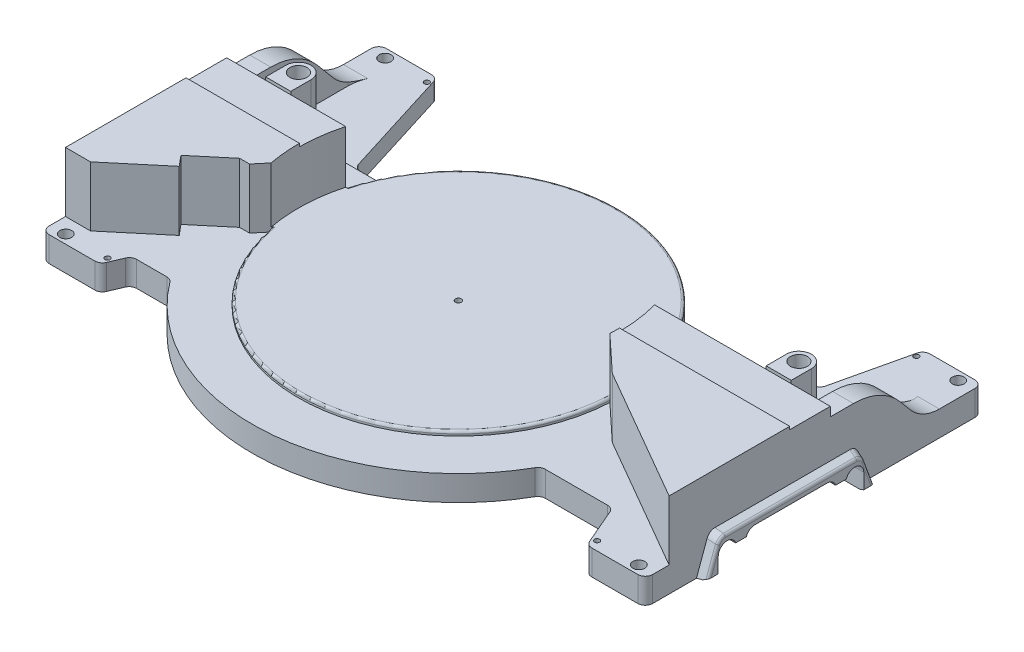
SolidWorks part; units mm, degrees
note: '?' marks a value the reader was unsure of.
ref_plane "Front Plane" through (0, 0, 0) normal (0, 0, 1) x (1, 0, 0)
ref_plane "Top Plane" through (0, 0, 0) normal (0, 1, 0) x (1, 0, 0)
ref_plane "Right Plane" through (0, 0, 0) normal (1, 0, 0) x (0, 0, -1)
sketch "Sketch1" plane through (0, 0, 0) normal (0, 1, 0) x (1, 0, 0)
  line L0 (330.2, 437.9007) -> (330.2, -96.542) construction
  line L1 (9.144, 0) -> (71.12, 0)
  line L3 (9.144, 358.648) -> (71.12, 358.648)
  line L7 (300.0375, 292.4565) -> (300.0375, 69.5569) construction
  line L8 (244.8786, 152.4) -> (359.3405, 152.4) construction
  line L9 (110.744, 231.648) -> (149.3493, 231.648)
  line L10 (450.7257, 231.648) -> (486.156, 231.648)
  line L11 (492.5022, 47.752) -> (568.706, 47.752)
  line L12 (651.256, 358.648) -> (651.256, 0)
  line L19 (9.144, 358.648) -> (9.144, 0)
  line L20 (81.28, 23.749) -> (122.7164, 23.749)
  line L21 (81.28, 23.749) -> (71.12, 0)
  line L22 (568.706, 47.752) -> (589.28, 0)
  line L23 (589.28, 358.648) -> (568.706, 269.748)
  line L24 (589.28, 0) -> (651.256, 0)
  line L25 (568.706, 269.748) -> (486.156, 231.648)
  line L26 (71.12, 358.648) -> (110.744, 231.648)
  line L27 (589.28, 358.648) -> (651.256, 358.648)
  arc A2 (450.7257, 231.648) -> (149.3493, 231.648) centre (300.0375, 152.4) ccw
  arc A3 (122.7164, 23.749) -> (492.5022, 47.752) centre (300.0375, 152.4) ccw
  point P4 (330.2, 179.324)
  dimension "D5" = 642.112
  dimension "D6" = 47.752
  dimension "D8" = 170.2562
  dimension "D4" = 219.075
  dimension "D2" = 358.648
  dimension "D7" = 127
  dimension "D9" = 290.8935
  dimension "D10" = 152.4
  dimension "D11" = 9.144
  dimension "D12" = 101.6
  dimension "D13" = 82.55
  dimension "D15" = 61.976
  dimension "D17" = 61.976
  dimension "D18" = 23.749
  dimension "D20" = 72.136
  dimension "D22" = 61.976
  dimension "D23" = 61.976
  dimension "D24" = 88.9
  dimension "D25" = 82.55
  dimension "D26" = 165.1
  dimension "D32" = 321.056
extrude "Boss-Extrude1" add sketch "Sketch1" along normal blind 20.6375
ref_axis "Axis1" through (300.0375, 49.3521, -152.4) along (0, -1, 0)?
ref_plane "Plane4" through (300.0375, 0, 0) normal (-1, 0, 0) x (0, -1, 0)
ref_plane "Plane5" through (73.8187, 0, 73.8187) normal (-0.7071, 0, -0.7071) x (0, -1, 0)
sketch "Sketch55" plane through (0, 0, 0) normal (0, -1, 0) x (1, 0, 0)
  line L0 (55, 0) -> (-55, 0) construction
  line L1 (0, -55) -> (0, 55) construction
  circle A0 centre (300.0375, -152.4) radius 12.7
  dimension "D1" = 25.4
  dimension "D2" = 152.4
  dimension "D3" = 300.0375
extrude "Cut-Extrude28" cut sketch "Sketch55" against normal through all
ref_plane "Plane1" through (0, 0, -145.923) normal (0, 0, 1) x (1, 0, 0)
ref_plane "Plane2" through (330.2, 0, 0) normal (1, 0, 0) x (0, 0, -1)
sketch "Sketch4" plane through (0, 20.6375, 0) normal (0, 1, 0) x (1, 0, 0)
  line L0 (9.144, 196.85) -> (9.144, 25.4)
  line L1 (651.256, 196.85) -> (609.727, 196.85)
  line L2 (9.144, 358.648) -> (9.144, 0) construction
  line L3 (9.144, 25.4) -> (35.7632, 25.4)
  line L4 (35.7632, 25.4) -> (87.0763, 68.4568)
  line L5 (87.0763, 68.4568) -> (77.8211, 79.4868)
  line L6 (77.8211, 79.4868) -> (111.7939, 107.9934)
  line L7 (111.7939, 107.9934) -> (122.3395, 107.9934)
  line L8 (122.3395, 107.9934) -> (132.809, 120.4704)
  line L9 (9.144, 25.4) -> (-70.9798, 120.8878) construction
  line L10 (9.144, 0) -> (71.12, 0) construction
  line L12 (300.0375, 152.4) -> (300.0375, 401.0132) construction
  line L16 (651.256, 196.85) -> (651.256, 25.4)
  line L17 (87.0763, 68.4568) -> (87.0763, 87.2528) construction
  line L18 (651.256, 0) -> (651.256, 358.648) construction
  line L19 (9.144, 196.85) -> (50.673, 196.85)
  line L21 (651.256, 25.4) -> (508.2752, 107.95)
  line L22 (508.2752, 107.95) -> (470.0587, 143.5875)
  line L23 (589.28, 0) -> (651.256, 0) construction
  line L24 (651.256, 358.648) -> (589.28, 358.648) construction
  line L25 (583.057, 218.313) -> (583.057, 196.85)
  line L26 (609.727, 218.313) -> (609.727, 196.85)
  line L27 (583.057, 196.85) -> (464.3819, 196.85)
  line L28 (9.144, 358.648) -> (651.256, 358.648) construction
  line L29 (330.2, 358.648) -> (330.2, 466.1211) construction
  line L30 (50.673, 218.313) -> (50.673, 196.85)
  line L31 (77.343, 218.313) -> (77.343, 196.85)
  line L32 (77.343, 196.85) -> (135.6931, 196.85)
  arc A0 (135.6931, 196.85) -> (132.809, 120.4704) centre (300.0375, 152.4) ccw
  arc A7 (464.3819, 196.85) -> (470.0587, 143.5875) centre (300.0375, 152.4) cw
  circle A8 centre (596.392, 218.313) radius 9.0932
  arc A9 (609.727, 218.313) -> (583.057, 218.313) centre (596.392, 218.313) ccw
  arc A10 (50.673, 218.313) -> (77.343, 218.313) centre (64.008, 218.313) cw
  circle A11 centre (64.008, 218.313) radius 9.0932
  point P22 (35.7632, 25.4)
  point P25 (87.0763, 68.4568)
  point P28 (9.144, 25.4)
  dimension "D6" = 40
  dimension "D9" = 18.796
  dimension "D10" = 131.7244
  dimension "D8" = 87.376
  dimension "D11" = 7.62
  dimension "D7" = 171.45
  dimension "D15" = 170.2494
  dimension "D23" = 18.1864
  dimension "D25" = 26.67
  dimension "D26" = 127
  dimension "D2" = 26.6192
  dimension "D4" = 14.3986
  dimension "D5" = 25.4
  dimension "D12" = 10
  dimension "D19" = 25.4
  dimension "D20" = 60
  dimension "D21" = 13
  dimension "D22" = 165.1
  dimension "D24" = 54.864
extrude "Boss-Extrude3" add sketch "Sketch4" along normal blind 71.5137
ref_plane "Plane3" through (300.0375, 0, 0) normal (1, 0, 0) x (0, 0, -1)
sketch "Sketch8" plane through (9.144, 0, 0) normal (-1, 0, 0) x (0, 0, 1)
  line L0 (-237.998, 0) -> (-223.9458, 38.608)
  line L1 (-223.9458, 38.608) -> (-67.9002, 38.608)
  line L3 (-67.9002, 38.608) -> (-53.848, 0)
  line L4 (-53.848, 0) -> (-237.998, 0)
  line L5 (-358.648, 0) -> (0, 0) construction
  line L6 (-223.9458, 38.608) -> (-223.9458, -28.336) construction
  line L7 (-67.9002, 38.608) -> (-67.9002, -28.336) construction
  line L8 (0, 20.6375) -> (0, 0) construction
  dimension "D1" = 38.608
  dimension "D2" = 20
  dimension "D3" = 20
  dimension "D4" = 184.15
  dimension "D5" = 53.848
sketch "Sketch15" plane through (0, 20.6375, 0) normal (0, 1, 0) x (1, 0, 0)
  line L15 (609.727, 196.85) -> (651.256, 196.85)
  line L17 (609.727, 196.85) -> (651.256, 196.85)
  line L18 (651.256, 196.85) -> (651.256, 358.648)
  line L19 (651.256, 358.648) -> (589.28, 358.648)
  line L20 (589.28, 358.648) -> (568.706, 269.748)
  line L21 (568.706, 269.748) -> (486.156, 231.648)
  line L22 (486.156, 231.648) -> (450.7257, 231.648)
  line L23 (149.3493, 231.648) -> (110.744, 231.648)
  line L24 (110.744, 231.648) -> (71.12, 358.648)
  line L25 (71.12, 358.648) -> (9.144, 358.648)
  line L26 (9.144, 358.648) -> (9.144, 196.85)
  line L28 (9.144, 196.85) -> (50.673, 196.85)
  line L30 (9.144, 196.85) -> (50.673, 196.85)
  line L32 (50.673, 196.85) -> (50.673, 218.313)
  line L35 (651.256, 196.85) -> (651.256, 358.648)
  line L36 (651.256, 358.648) -> (589.28, 358.648)
  line L37 (589.28, 358.648) -> (568.706, 269.748)
  line L38 (568.706, 269.748) -> (486.156, 231.648)
  line L39 (486.156, 231.648) -> (450.7257, 231.648)
  line L40 (149.3493, 231.648) -> (110.744, 231.648)
  line L41 (110.744, 231.648) -> (71.12, 358.648)
  line L42 (71.12, 358.648) -> (9.144, 358.648)
  line L43 (9.144, 358.648) -> (9.144, 196.85)
  line L51 (50.673, 196.85) -> (50.673, 218.313)
  line L55 (77.343, 218.313) -> (77.343, 196.85)
  line L56 (77.343, 218.313) -> (77.343, 196.85)
  line L57 (77.343, 196.85) -> (135.6931, 196.85)
  line L58 (77.343, 196.85) -> (135.6931, 196.85)
  line L59 (464.3819, 196.85) -> (583.057, 196.85)
  line L60 (464.3819, 196.85) -> (583.057, 196.85)
  line L61 (583.057, 196.85) -> (583.057, 218.313)
  line L62 (583.057, 196.85) -> (583.057, 218.313)
  line L63 (609.727, 218.313) -> (609.727, 196.85)
  line L64 (609.727, 218.313) -> (609.727, 196.85)
  line L115 (651.256, 0) -> (651.256, 25.4)
  line L116 (651.256, 0) -> (651.256, 25.4)
  line L117 (651.256, 25.4) -> (508.2752, 107.95)
  line L118 (651.256, 25.4) -> (508.2752, 107.95)
  line L119 (508.2752, 107.95) -> (470.0587, 143.5875)
  line L120 (508.2752, 107.95) -> (470.0587, 143.5875)
  line L121 (132.809, 120.4704) -> (122.3395, 107.9934)
  line L122 (132.809, 120.4704) -> (122.3395, 107.9934)
  line L123 (122.3395, 107.9934) -> (111.7939, 107.9934)
  line L124 (122.3395, 107.9934) -> (111.7939, 107.9934)
  line L125 (111.7939, 107.9934) -> (77.8211, 79.4868)
  line L126 (111.7939, 107.9934) -> (77.8211, 79.4868)
  line L127 (77.8211, 79.4868) -> (87.0763, 68.4568)
  line L128 (77.8211, 79.4868) -> (87.0763, 68.4568)
  line L129 (87.0763, 68.4568) -> (35.7632, 25.4)
  line L130 (87.0763, 68.4568) -> (35.7632, 25.4)
  line L131 (35.7632, 25.4) -> (9.144, 25.4)
  line L132 (35.7632, 25.4) -> (9.144, 25.4)
  line L133 (9.144, 25.4) -> (9.144, 0)
  line L134 (9.144, 25.4) -> (9.144, 0)
  line L135 (9.144, 0) -> (71.12, 0)
  line L136 (9.144, 0) -> (71.12, 0)
  line L137 (71.12, 0) -> (81.28, 23.749)
  line L138 (71.12, 0) -> (81.28, 23.749)
  line L139 (81.28, 23.749) -> (122.7164, 23.749)
  line L140 (81.28, 23.749) -> (122.7164, 23.749)
  line L141 (492.5022, 47.752) -> (568.706, 47.752)
  line L142 (492.5022, 47.752) -> (568.706, 47.752)
  line L143 (568.706, 47.752) -> (589.28, 0)
  line L144 (568.706, 47.752) -> (589.28, 0)
  line L145 (589.28, 0) -> (651.256, 0)
  line L146 (589.28, 0) -> (651.256, 0)
  arc A2 (77.343, 218.313) -> (50.673, 218.313) centre (64.008, 218.313) ccw
  arc A4 (450.7257, 231.648) -> (149.3493, 231.648) centre (300.0375, 152.4) ccw
  arc A7 (77.343, 218.313) -> (50.673, 218.313) centre (64.008, 218.313) ccw
  arc A8 (450.7257, 231.648) -> (149.3493, 231.648) centre (300.0375, 152.4) ccw
  arc A13 (470.0587, 143.5875) -> (464.3819, 196.85) centre (300.0375, 152.4) ccw
  arc A17 (609.727, 218.313) -> (583.057, 218.313) centre (596.392, 218.313) ccw
  arc A19 (609.727, 218.313) -> (583.057, 218.313) centre (596.392, 218.313) ccw
  arc A28 (470.0587, 143.5875) -> (464.3819, 196.85) centre (300.0375, 152.4) ccw
  arc A29 (135.6931, 196.85) -> (132.809, 120.4704) centre (300.0375, 152.4) ccw
  arc A30 (135.6931, 196.85) -> (132.809, 120.4704) centre (300.0375, 152.4) ccw
  arc A31 (122.7164, 23.749) -> (492.5022, 47.752) centre (300.0375, 152.4) ccw
  arc A32 (122.7164, 23.749) -> (492.5022, 47.752) centre (300.0375, 152.4) ccw
  dimension "D1" = 0
extrude "Boss-Extrude9" add sketch "Sketch15" along normal blind 7.8486
sketch "Sketch13" plane through (0, 20.6375, 0) normal (0, 1, 0) x (1, 0, 0)
  line L0 (651.256, 324.612) -> (623.824, 324.612)
  line L1 (651.256, 196.85) -> (651.256, 358.648) construction
  line L3 (629.031, 303.784) -> (629.031, 196.85)
  line L4 (651.256, 196.85) -> (609.727, 196.85) construction
  line L5 (629.031, 196.85) -> (651.256, 196.85)
  line L6 (651.256, 196.85) -> (651.256, 324.612)
  line L7 (651.256, 358.648) -> (589.28, 358.648) construction
  line L8 (9.144, 358.648) -> (651.256, 358.648) construction
  line L9 (330.2, 358.648) -> (330.2, 407.4216) construction
  line L10 (9.144, 196.85) -> (9.144, 324.612)
  line L11 (31.369, 196.85) -> (9.144, 196.85)
  line L12 (31.369, 303.784) -> (31.369, 196.85)
  line L13 (9.144, 324.612) -> (36.576, 324.612)
  line L14 (9.144, 358.648) -> (9.144, 196.85) construction
  arc A0 (629.031, 303.784) -> (623.824, 324.612) centre (584.7715, 303.784) ccw
  arc A1 (31.369, 303.784) -> (36.576, 324.612) centre (75.6285, 303.784) cw
  dimension "D1" = 22.225
  dimension "D2" = 34.036
  dimension "D3" = 54.864
  dimension "D4" = 27.432
extrude "Boss-Extrude8" add sketch "Sketch13" along normal blind 58.5978
sketch "Sketch14" plane through (651.256, 0, 0) normal (1, 0, 0) x (0, 0, -1)
  line L0 (358.648, 28.4861) -> (358.648, 0) construction
  line L1 (358.648, 28.4861) -> (312.8748, 28.4861)
  line L2 (196.85, 79.2353) -> (324.612, 79.2353) construction
  line L3 (221.4505, 79.2353) -> (196.85, 79.2353)
  line L4 (196.85, 79.2353) -> (196.85, 92.1512)
  line L5 (196.85, 92.1512) -> (358.648, 92.1512)
  line L6 (358.648, 92.1512) -> (358.648, 28.4861)
  line L8 (271.167, 56.0521) -> (282.3565, 42.717)
  line L9 (324.612, 28.4861) -> (358.648, 28.4861) construction
  arc A0 (312.8748, 28.4861) -> (282.3565, 42.717) centre (312.8748, 68.3249) cw
  arc A2 (271.167, 56.0521) -> (221.4505, 79.2353) centre (221.4505, 14.335) ccw
  point P5 (251.714, 79.2353)
  dimension "D4" = 64.9003
  dimension "D5" = 39.8388
  dimension "D2" = 50
  dimension "D3" = 54.864
extrude "Cut-Extrude3" cut sketch "Sketch14" against normal blind 30.48
sketch "Sketch16" plane through (0, 28.4861, 0) normal (0, 1, 0) x (1, 0, 0)
  line L1 (31.369, 223.774) -> (51.8425, 223.774)
  line L2 (76.1735, 223.774) -> (145.4716, 223.774)
  line L22 (628.0873, 312.8748) -> (651.256, 312.8748)
  line L23 (651.256, 312.8748) -> (651.256, 358.648)
  line L24 (651.256, 358.648) -> (589.28, 358.648)
  line L25 (589.28, 358.648) -> (568.706, 269.748)
  line L26 (568.706, 269.748) -> (486.156, 231.648)
  line L27 (486.156, 231.648) -> (450.7257, 231.648)
  line L28 (149.3493, 231.648) -> (110.744, 231.648)
  line L29 (110.744, 231.648) -> (71.12, 358.648)
  line L30 (71.12, 358.648) -> (9.144, 358.648)
  line L31 (9.144, 358.648) -> (9.144, 324.612)
  line L32 (9.144, 324.612) -> (36.576, 324.612)
  line L33 (31.369, 303.784) -> (31.369, 196.85)
  line L34 (31.369, 196.85) -> (50.673, 196.85)
  line L35 (50.673, 196.85) -> (50.673, 218.313)
  line L36 (77.343, 218.313) -> (77.343, 196.85)
  line L37 (77.343, 196.85) -> (135.6931, 196.85)
  line L38 (464.3819, 196.85) -> (583.057, 196.85)
  line L39 (583.057, 196.85) -> (583.057, 218.313)
  line L40 (609.727, 218.313) -> (609.727, 196.85)
  line L41 (609.727, 196.85) -> (629.031, 196.85)
  line L42 (629.031, 196.85) -> (629.031, 303.784)
  line L49 (149.357, 231.648) -> (110.744, 231.648)
  line L50 (110.744, 231.648) -> (71.12, 358.648)
  line L51 (71.12, 358.648) -> (9.144, 358.648)
  line L52 (9.144, 358.648) -> (9.144, 324.612)
  line L53 (9.144, 324.612) -> (36.576, 324.612)
  line L54 (31.369, 303.784) -> (31.369, 223.774)
  line L82 (132.809, 120.4704) -> (122.3395, 107.9934)
  line L84 (122.3395, 107.9934) -> (111.7939, 107.9934)
  line L86 (111.7939, 107.9934) -> (77.8211, 79.4868)
  line L88 (77.8211, 79.4868) -> (87.0763, 68.4568)
  line L90 (87.0763, 68.4568) -> (35.7632, 25.4)
  line L92 (35.7632, 25.4) -> (9.144, 25.4)
  line L94 (9.144, 25.4) -> (9.144, 0)
  line L96 (9.144, 0) -> (71.12, 0)
  line L98 (71.12, 0) -> (81.28, 23.749)
  line L100 (81.28, 23.749) -> (122.7164, 23.749)
  line L102 (492.5022, 47.752) -> (568.706, 47.752)
  line L104 (568.706, 47.752) -> (589.28, 0)
  line L106 (589.28, 0) -> (651.256, 0)
  line L108 (651.256, 0) -> (651.256, 25.4)
  line L110 (651.256, 25.4) -> (508.2752, 107.95)
  line L112 (508.2752, 107.95) -> (470.0587, 143.5875)
  arc A0 (135.6931, 196.85) -> (132.809, 120.4704) centre (300.0375, 152.4) ccw construction
  arc A1 (149.357, 231.648) -> (145.4716, 223.774) centre (300.0375, 152.4) ccw
  arc A6 (629.031, 303.784) -> (628.0873, 312.8748) centre (584.7715, 303.784) ccw
  arc A7 (450.7257, 231.648) -> (149.3493, 231.648) centre (300.0375, 152.4) ccw
  arc A8 (36.576, 324.612) -> (31.369, 303.784) centre (75.6285, 303.784) ccw
  arc A9 (77.343, 218.313) -> (50.673, 218.313) centre (64.008, 218.313) ccw
  arc A10 (135.6931, 196.85) -> (132.809, 120.4704) centre (300.0375, 152.4) ccw
  arc A11 (609.727, 218.313) -> (583.057, 218.313) centre (596.392, 218.313) ccw
  arc A14 (36.576, 324.612) -> (31.369, 303.784) centre (75.6285, 303.784) ccw
  arc A15 (76.1735, 223.774) -> (51.8425, 223.774) centre (64.008, 218.313) ccw
  arc A23 (122.7164, 23.749) -> (492.5022, 47.752) centre (300.0375, 152.4) ccw
  arc A25 (470.0587, 143.5875) -> (464.3819, 196.85) centre (300.0375, 152.4) ccw
  dimension "D1" = 0
  dimension "D2" = 134.874
extrude "Cut-Extrude4" cut sketch "Sketch16" against normal blind 7.8486
sketch "Sketch17" plane through (9.144, 0, 0) normal (-1, 0, 0) x (0, 0, 1)
  line L0 (-196.85, 92.1512) -> (-196.85, 79.2353)
  line L2 (-271.167, 56.0521) -> (-282.3565, 42.717) construction
  line L4 (-271.167, 56.0521) -> (-287.8797, 36.1347)
  line L5 (-358.648, 20.6375) -> (-358.648, 92.1512)
  line L6 (-358.648, 92.1512) -> (-196.85, 92.1512)
  line L7 (-25.4, 92.1512) -> (-196.85, 92.1512) construction
  line L8 (-324.612, 79.2353) -> (-196.85, 79.2353) construction
  line L9 (-221.4505, 79.2353) -> (-196.85, 79.2353)
  line L10 (-358.648, 20.6375) -> (-324.612, 20.6375) construction
  line L11 (-358.648, 20.6375) -> (-321.1135, 20.6375)
  line L12 (-358.648, 0) -> (0, 0) construction
  arc A0 (-321.1135, 20.6375) -> (-287.8797, 36.1347) centre (-321.1135, 64.0211) ccw
  arc A1 (-221.4505, 79.2353) -> (-271.167, 56.0521) centre (-221.4505, 14.335) ccw construction
  arc A3 (-221.4505, 79.2353) -> (-271.167, 56.0521) centre (-221.4505, 14.335) ccw
  dimension "D2" = 43.3836
  dimension "D1" = 56.0521
extrude "Cut-Extrude6" cut sketch "Sketch17" against normal blind 27.432
fillet "Fillet1" radius 7.9375 17 edges at (651.256, 14.2431, -358.648) (589.28, 14.2431, -358.648) (568.706, 14.2431, -269.748) (486.156, 14.2431, -231.648) (450.7257, 14.2431, -231.648) (149.3493, 10.3188, -231.648) (110.744, 10.3188, -231.648) (71.12, 10.3188, -358.648) (9.144, 14.2431, 0) (71.12, 14.2431, 0) (81.28, 14.2431, -23.749) (122.7164, 14.2431, -23.749) (492.5022, 14.2431, -47.752) (568.706, 14.2431, -47.752) (589.28, 14.2431, 0) (9.144, 10.3188, -358.648) (651.256, 14.2431, 0)
extrude "Boss-Extrude5" add sketch "Sketch8" along normal blind 9.144 draft 20
fillet "Fillet2" radius 9.525 2 edges at (4.572, 36.9439, -69.0654) (4.572, 36.9439, -222.7806)
fillet "Fillet3" radius 3.175 5 edges at (0, 16.3594, -63.3441) (0, 33.6815, -71.3497) (0, 35.2799, -145.923) (0, 33.6815, -220.4963) (0, 16.3594, -228.5019)
sketch "Sketch6" plane through (0, 0, 0) normal (-1, 0, 0) x (0, 0, 1)
  line L1 (-223.3477, 19.558) -> (-223.3477, 0)
  line L3 (-223.3477, 0) -> (-68.4983, 0)
  line L4 (-68.4983, 0) -> (-68.4983, 19.558)
  line L6 (-213.8227, 19.558) -> (-184.3107, 19.558) construction
  line L7 (-184.3107, 19.558) -> (-107.5353, 19.558) construction
  line L8 (-107.5353, 19.558) -> (-78.0233, 19.558) construction
  line L12 (-204.7817, 22.5557) -> (-193.3517, 22.5557)
  line L14 (-98.4943, 22.5557) -> (-87.0643, 22.5557)
  line L16 (-184.3107, 29.083) -> (-107.5353, 29.083)
  line L17 (-221.6154, 35.2799) -> (-234.4563, 0) construction
  line L21 (-57.3897, 0) -> (-70.2306, 35.2799) construction
  line L22 (-350.7105, 0) -> (-237.998, 0) construction
  arc A3 (-98.4943, 22.5557) -> (-107.5353, 29.083) centre (-107.5353, 19.558) ccw
  arc A4 (-204.7817, 22.5557) -> (-223.3477, 19.558) centre (-213.8227, 19.558) ccw
  arc A5 (-68.4983, 19.558) -> (-87.0643, 22.5557) centre (-78.0233, 19.558) ccw
  arc A6 (-184.3107, 29.083) -> (-193.3517, 22.5557) centre (-184.3107, 19.558) ccw
  dimension "D1" = 3.175
  dimension "D2" = 3.175
  dimension "D4" = 11.43
  dimension "D6" = 9.525
  dimension "D3" = 19.558
  dimension "D5" = 11.43
  dimension "D7" = 22.5557
extrude "Cut-Extrude2" cut sketch "Sketch6" against normal blind 38.1
mirror "Mirror3" about plane through (330.2, 0, 0) normal (1, 0, 0) of "Cut-Extrude2", "Fillet3", "Fillet2", "Boss-Extrude5"
sketch "Sketch20" plane through (0, 0, 0) normal (0, -1, 0) x (1, 0, 0)
  circle A0 centre (300.0375, -152.4) radius 170.2562
  arc A1 (151.5519, -235.7019) -> (448.5231, -235.7019) centre (300.0375, -152.4) ccw construction
extrude "Boss-Extrude12" add sketch "Sketch20" against normal blind 33.02
sketch "Sketch54" plane through (0, 92.1512, 0) normal (0, 1, 0) x (1, 0, 0)
  line L0 (651.256, 74.1674) -> (651.256, 217.6786) construction
  line L1 (9.144, 196.85) -> (651.256, 196.85)
  line L2 (9.144, 196.85) -> (9.144, 153.67)
  line L3 (9.144, 153.67) -> (651.256, 153.67)
  line L4 (651.256, 196.85) -> (651.256, 153.67)
  line L5 (9.144, 196.85) -> (651.256, 153.67) construction
  line L6 (9.144, 153.67) -> (651.256, 196.85) construction
  line L7 (9.144, 74.1674) -> (9.144, 217.6786) construction
  line L8 (50.673, 196.85) -> (9.144, 196.85) construction
  point P4 (330.2, 175.26)
  dimension "D1" = 43.18
extrude "Cut-Extrude23" cut sketch "Sketch54" against normal blind 3.175
fillet "Fillet10" radius 2.54 1 edges at (311.6804, 33.02, 17.4576)
sketch "Sketch56" plane through (0, 0, 0) normal (0, -1, 0) x (1, 0, 0)
  line L0 (9.144, -53.848) -> (9.144, -7.9375) construction
  line L1 (25.4, -9.4488) -> (635, -9.4488) construction
  line L2 (25.4, -9.4488) -> (25.4, -349.1738) construction
  line L3 (25.4, -349.1738) -> (635, -349.1738) construction
  line L4 (635, -9.4488) -> (635, -349.1738) construction
  line L5 (69.85, 27.1826) -> (69.85, -394.9535) construction
  line L6 (590.55, 35.9285) -> (590.55, -403.1163) construction
  line L8 (594.503, 0) -> (643.3185, 0) construction
  circle A0 centre (25.4, -9.4488) radius 6.35
  circle A1 centre (25.4, -349.1738) radius 6.35
  circle A2 centre (635, -9.4488) radius 6.35
  circle A3 centre (635, -349.1738) radius 6.35
  circle A4 centre (69.85, -9.4488) radius 2.7813
  circle A5 centre (69.85, -349.1738) radius 2.7813
  circle A6 centre (590.55, -9.4488) radius 2.7813
  circle A7 centre (590.55, -349.1738) radius 2.7813
  point P9 (618.9108, 0)
  dimension "D5" = 12.7
  dimension "D8" = 5.5626
  dimension "D1" = 609.6
  dimension "D2" = 339.725
  dimension "D3" = 16.256
  dimension "D4" = 9.4488
  dimension "D6" = 44.45
  dimension "D7" = 44.45
extrude "Cut-Extrude29" cut sketch "Sketch56" against normal through all
sketch "Sketch57" plane through (0, 0, 0) normal (0, 0, 1) x (1, 0, 0)
  line L0 (35.7632, 92.1512) -> (87.0763, 92.1512) construction
  line L1 (-25.4, 1.7272) -> (685.8, 1.7272)
  line L2 (-25.4, 1.7272) -> (-25.4, -23.6728)
  line L3 (-25.4, -23.6728) -> (685.8, -23.6728)
  line L4 (685.8, 1.7272) -> (685.8, -23.6728)
  line L5 (660.4, 29.1305) -> (660.4, 3.3281) construction
  point P6 (61.4198, 92.1512)
  dimension "D1" = 90.424
  dimension "D2" = 25.4
  dimension "D3" = 25.4
  dimension "D4" = 25.4
extrude "Cut-Extrude30" cut sketch "Sketch57" against normal through all both and the other way through all
sketch "Sketch58" plane through (0, 1.7272, 0) normal (0, -1, 0) x (1, 0, 0)
  line L0 (300.0375, 114.3951) -> (300.0375, -114.3951) construction
  line L1 (-6.9816, 154.6191) -> (154.6191, -6.9816) construction
  circle A0 centre (300.0375, -152.4) radius 3.175
  dimension "D1" = 6.35
extrude "Cut-Extrude31" cut sketch "Sketch58" against normal through all
